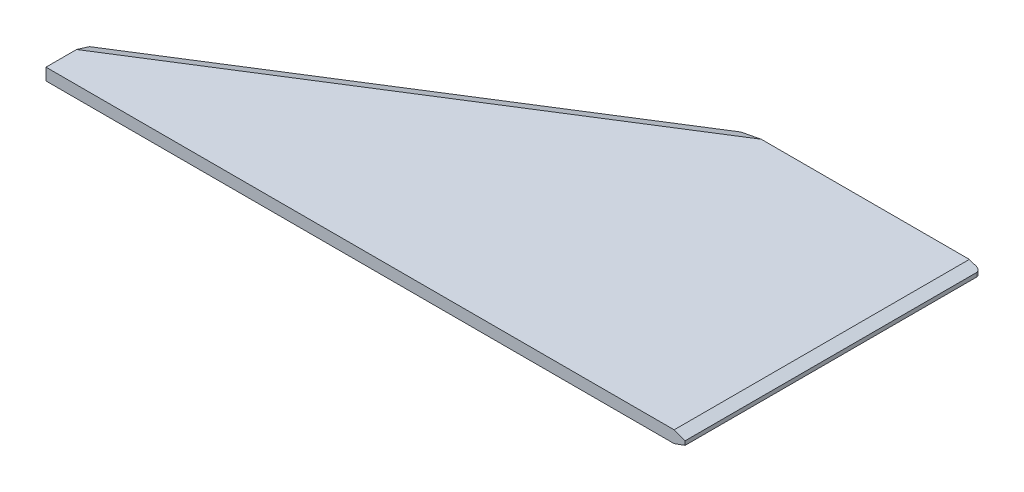
SolidWorks part; units mm, degrees
material "A-Glass Fiber"
ref_plane "Front Plane" through (0, 0, 0) normal (0, 0, 1) x (1, 0, 0)
ref_plane "Top Plane" through (0, 0, 0) normal (0, 1, 0) x (1, 0, 0)
ref_plane "Right Plane" through (0, 0, 0) normal (1, 0, 0) x (0, 0, -1)
sketch "Sketch1" plane through (0, 0, 0) normal (0, 1, 0) x (1, 0, 0)
  line L0 (0, 0) -> (0, 10.9)
  line L1 (0, 10.9) -> (100, 73.9)
  line L2 (100, 73.9) -> (160, 73.9)
  line L3 (160, 73.9) -> (160, 10.9)
  line L4 (160, 10.9) -> (160, 0)
  line L5 (160, 0) -> (152.5, 0)
  line L6 (152.5, 0) -> (152.5, 9.4) construction
  line L7 (152.5, 9.4) -> (149, 9.4) construction
  line L8 (149, 9.4) -> (149, 0) construction
  line L9 (149, 0) -> (0, 0)
  line L10 (-989.0676, -29) -> (49010.9324, -29) construction
  line L11 (-1000, 0) -> (49000, 0) construction
  line L12 (-999.3384, -58) -> (49000.6616, -58) construction
  line L13 (0, 0) -> (0, -58) construction
  line L14 (149, 0) -> (152.5, 0)
  point P15 (0, -29)
  dimension "D1" = 60
  dimension "D2" = 160
  dimension "D3" = 1.5
  dimension "D4" = 100
  dimension "D5" = 63
  dimension "D6" = 79.8
  dimension "D7" = 58
  dimension "D8" = 3.5
  dimension "D9" = 7.5
extrude "Boss-Extrude1" add sketch "Sketch1" along normal blind 3
chamfer "Chamfer1" distance 1 angle 70 2 edges at (160, 3, -36.95) (50, 3, -42.4) first distance on face at (160, 1.5, -36.95) first distance on face at (50, 1.5, -42.4)
chamfer "Chamfer2" distance 1 angle 70 2 edges at (50, 0, -42.4) (160, 0, -36.95) first distance on face at (50, 1, -42.4) first distance on face at (160, 1, -36.95)
fillet "Fillet1" radius 1 1 edges at (160, 1.5, -73.9)
